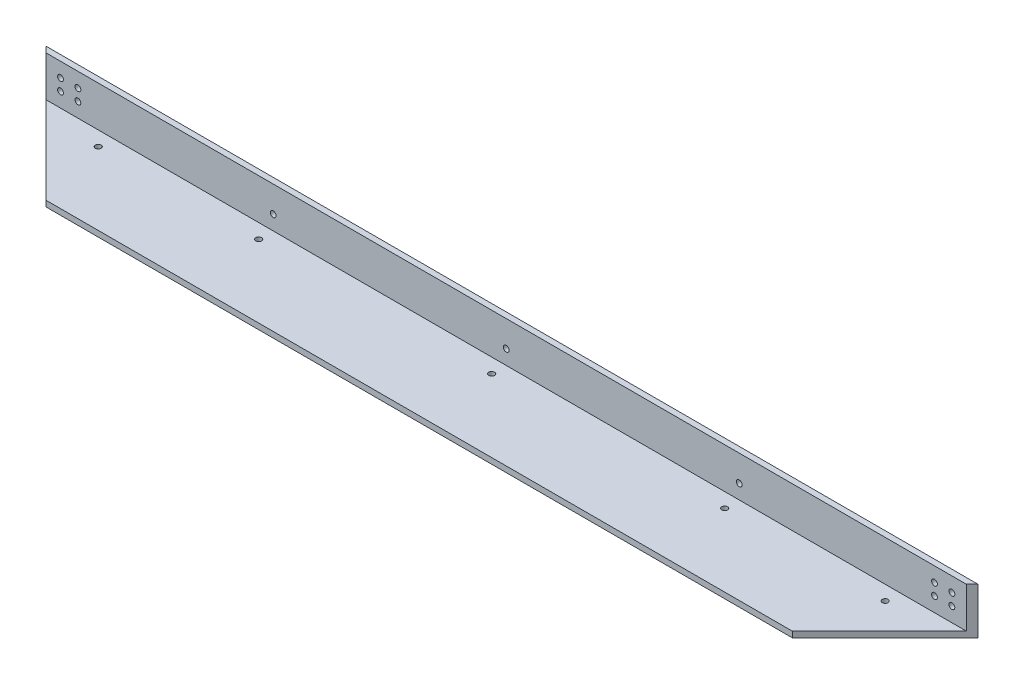
SolidWorks part; units mm, degrees
ref_plane "Front Plane" through (0, 0, 0) normal (0, 0, 1) x (1, 0, 0)
ref_plane "Top Plane" through (0, 0, 0) normal (0, 1, 0) x (1, 0, 0)
ref_plane "Right Plane" through (0, 0, 0) normal (1, 0, 0) x (0, 0, -1)
sketch "Sketch1" plane through (0, 0, 0) normal (1, 0, 0) x (0, 0, -1)
  line L0 (0, 0) -> (-50.8, 0)
  line L1 (-50.8, 0) -> (-50.8, 3.175)
  line L2 (-50.8, 3.175) -> (-3.175, 3.175)
  line L3 (-3.175, 3.175) -> (-3.175, 25.4)
  line L4 (-3.175, 25.4) -> (0, 25.4)
  line L5 (0, 25.4) -> (0, 0)
  dimension "LHeight" = 25.4
  dimension "LWidth" = 50.8
  dimension "LMaterialThickness" = 3.175
  dimension "D1" = 47.625
  dimension "D2" = 22.225
  dimension "D3" = 3.175
extrude "Boss-Extrude1" add sketch "Sketch1" along normal blind 510
chamfer "Chamfer6" distance 50.8 angle 45 1 edges at (510, 1.5875, 50.8)
chamfer "Chamfer7" distance 50.8 angle 45 1 edges at (0, 1.5875, 50.8)
sketch "SideHoles-Sketch2" plane through (0, 0, 0) normal (0, 0, -1) x (-1, 0, 0)
  line L0 (0, 0) -> (0, 25.4) construction
  line L1 (-510, 0) -> (0, 0) construction
  line L2 (-510, 0) -> (-510, 25.4) construction
  circle A0 centre (-498.8875, 17.4625) radius 1.5875
  circle A1 centre (-489.3625, 17.4625) radius 1.5875
  circle A2 centre (-20.6375, 17.4625) radius 1.5875
  circle A3 centre (-11.1125, 17.4625) radius 1.5875
  circle A4 centre (-11.1125, 11.1125) radius 1.5875
  circle A5 centre (-20.6375, 11.1125) radius 1.5875
  circle A6 centre (-489.3625, 11.1125) radius 1.5875
  circle A7 centre (-498.8875, 11.1125) radius 1.5875
  circle A8 centre (-382.5, 11.1125) radius 1.5875
  circle A9 centre (-255, 11.1125) radius 1.5875
  circle A10 centre (-127.5, 11.1125) radius 1.5875
  dimension "D5" = 3.175
  dimension "D1" = 11.1125
  dimension "D2" = 20.6375
  dimension "D3" = 11.1125
  dimension "D4" = 20.6375
  dimension "D6" = 7.9375
  dimension "D7" = 11.1125
  dimension "D8" = 127.5
  dimension "D9" = 127.5
  dimension "D10" = 127.5
extrude "SideHoles-Cut-Extrude2" cut sketch "SideHoles-Sketch2" against normal through all
sketch "BottomHoles-Sketch2" plane through (0, 0, 0) normal (0, -1, 0) x (1, 0, 0)
  line L0 (510, 0) -> (0, 0) construction
  circle A0 centre (39.6875, 11.1125) radius 1.5875
  circle A1 centre (470.3125, 11.1125) radius 1.5875
  circle A2 centre (127.5, 11.1125) radius 1.5875
  circle A3 centre (255, 11.1125) radius 1.5875
  circle A4 centre (382.5, 11.1125) radius 1.5875
  dimension "D1" = 11.1125
  dimension "D4" = 3.175
  dimension "D2" = 39.6875
  dimension "D3" = 39.6875
  dimension "D5" = 127.5
  dimension "D6" = 127.5
  dimension "D7" = 127.5
extrude "BottomHoles-Cut-Extrude1" cut sketch "BottomHoles-Sketch2" against normal through all
equation "\"LowerRailWidth\"= 2.00in"
equation "\"LowerRailHeight\"= 1.00in"
equation "\"RailThickness\"= .125in'Spec"
equation "\"SideRailHoleX1FromSide\"= \"HoleOffsetFromSide\""
equation "\"SideRailHoleX2FromSide\"= \"VSWidth\" - \"HoleOffsetFromEdge\" - \"RailThickness\"'Equals 20.6375"
equation "\"SideRailHoleY1FromEdge\"= \"HoleOffsetFromEdge\""
equation "\"FrontBackRailLength\"= 510mm"
equation "\"VSWidth\"= 1.25in'Spec"
equation "\"HoleOffsetFromEdge\"= \"RailThickness\" * 2.5"
equation "\"HoleOffsetFromSide\"= \"RailThickness\" * 3.5"
equation "\"SideRailHoleY2FromSide\"= \"HoleOffsetFromSide\""
equation "\"FasteningHoleDiameter\"= .125in"
equation "\"D1@Boss-Extrude1\"=\"FrontBackRailLength\""
equation "\"D1@Chamfer6\"=\"LowerRailWidth\""
equation "\"D1@Chamfer7\"=\"LowerRailWidth\""
equation "\"D1@SideHoles-Sketch2\" = \"SideRailHoleX1FromSide\""
equation "\"D2@SideHoles-Sketch2\" = \"SideRailHoleX2FromSide\""
equation "\"D3@SideHoles-Sketch2\" = \"SideRailHoleX1FromSide\""
equation "\"D4@SideHoles-Sketch2\" = \"SideRailHoleX2FromSide\""
equation "\"D5@SideHoles-Sketch2\" = \"FasteningHoleDiameter\""
equation "\"D6@SideHoles-Sketch2\" = \"SideRailHoleY1FromEdge\""
equation "\"D7@SideHoles-Sketch2\" = \"SideRailHoleY2FromSide\""
equation "\"LHeight@Sketch1\"=\"LowerRailHeight\""
equation "\"LWidth@Sketch1\"=\"LowerRailWidth\""
equation "\"LowerCornerBlockWidth\"= \"LowerRailWidth\" - \"RailThickness\" * 2'Room for left front stepper"
equation "\"D1@BottomHoles-Sketch2\"=\"LowerCornerBlockY1FromSide\""
equation "\"D2@BottomHoles-Sketch2\"=\"LowerCornerBlockX1FromSide\""
equation "\"D3@BottomHoles-Sketch2\"=\"LowerCornerBlockX1FromSide\""
equation "\"D4@BottomHoles-Sketch2\" = \"FasteningHoleDiameter\""
equation "\"LowerCornerBlockX1FromSide\"= \"LowerCornerBlockWidth\" - \"HoleOffsetFromEdge\" + \"RailThickness\""
equation "\"LowerCornerBlockY1FromSide\"= \"HoleOffsetFromSide\""
equation "\"FrontOrBackEnclosureOffsets\"= \"FrontBackRailLength\" / 4"
equation "\"D5@BottomHoles-Sketch2\"=\"FrontOrBackEnclosureOffsets\""
equation "\"D6@BottomHoles-Sketch2\"=\"FrontOrBackEnclosureOffsets\""
equation "\"D7@BottomHoles-Sketch2\"=\"FrontOrBackEnclosureOffsets\""
equation "\"D8@SideHoles-Sketch2\"=\"FrontOrBackEnclosureOffsets\""
equation "\"D9@SideHoles-Sketch2\"=\"FrontOrBackEnclosureOffsets\""
equation "\"D10@SideHoles-Sketch2\"=\"FrontOrBackEnclosureOffsets\""
